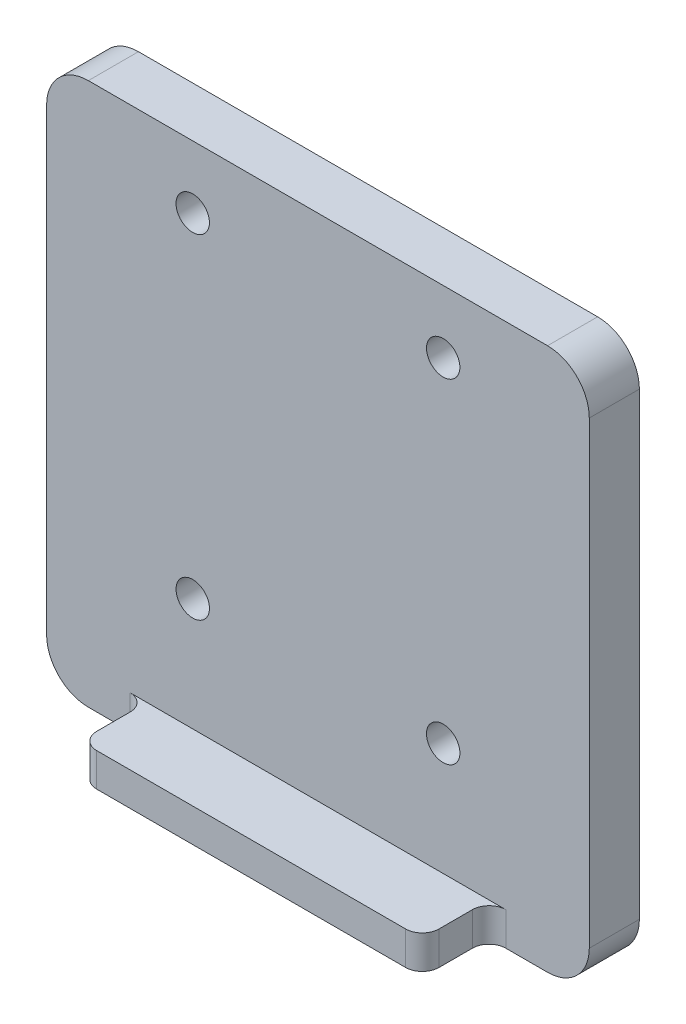
SolidWorks part; units mm, degrees
ref_plane "Front Plane" through (0, 0, 0) normal (0, 0, 1) x (1, 0, 0)
ref_plane "Top Plane" through (0, 0, 0) normal (0, 1, 0) x (1, 0, 0)
ref_plane "Right Plane" through (0, 0, 0) normal (1, 0, 0) x (0, 0, -1)
sketch "Sketch1" plane through (0, 0, 0) normal (0, 0, 1) x (1, 0, 0)
  line L1 (-32.5, 32.5) -> (32.5, 32.5)
  line L2 (-32.5, 32.5) -> (-32.5, -32.5)
  line L3 (-32.5, -32.5) -> (32.5, -32.5)
  line L4 (32.5, 32.5) -> (32.5, -32.5)
  line L5 (-32.5, 32.5) -> (32.5, -32.5) construction
  line L6 (-32.5, -32.5) -> (32.5, 32.5) construction
  point P0 (0, 0)
  dimension "D1" = 65
  dimension "D2" = 65
extrude "Boss-Extrude1" add sketch "Sketch1" along normal blind 6
fillet "Fillet1" radius 5 4 edges at (32.5, -32.5, 3) (-32.5, -32.5, 3) (32.5, 32.5, 3) (-32.5, 32.5, 3)
sketch "Sketch2" plane through (0, 0, 6) normal (0, 0, 1) x (1, 0, 0)
  line L0 (-27.5, -32.5) -> (27.5, -32.5) construction
  line L1 (-20.5, -32.5) -> (20.5, -32.5)
  line L2 (-20.5, -32.5) -> (-20.5, -28.5)
  line L3 (-20.5, -28.5) -> (20.5, -28.5)
  line L4 (20.5, -32.5) -> (20.5, -28.5)
  line L5 (0, 0) -> (0, -28.5) construction
  dimension "D1" = 41
  dimension "D2" = 4
extrude "Boss-Extrude2" add sketch "Sketch2" along normal blind 8
fillet "Fillet2" radius 2 4 edges at (20.5, -30.5, 6) (20.5, -30.5, 14) (-20.5, -30.5, 14) (-20.5, -30.5, 6)
sketch "Sketch3" plane through (0, 0, 0) normal (0, 0, -1) x (-1, 0, 0)
  line L0 (-15, 25) -> (15, -15) construction
  line L1 (-15, 25) -> (15, 25) construction
  line L2 (-15, 25) -> (-15, -15) construction
  line L3 (-15, -15) -> (15, -15) construction
  line L4 (15, 25) -> (15, -15) construction
  line L5 (0, 0) -> (0, 5) construction
  circle A0 centre (-15, 25) radius 2
  circle A1 centre (15, 25) radius 2
  circle A2 centre (-15, -15) radius 2
  circle A3 centre (15, -15) radius 2
  dimension "D1" = 4
  dimension "D2" = 40
  dimension "D3" = 30
  dimension "D4" = 5
extrude "Cut-Extrude1" cut sketch "Sketch3" against normal through all
